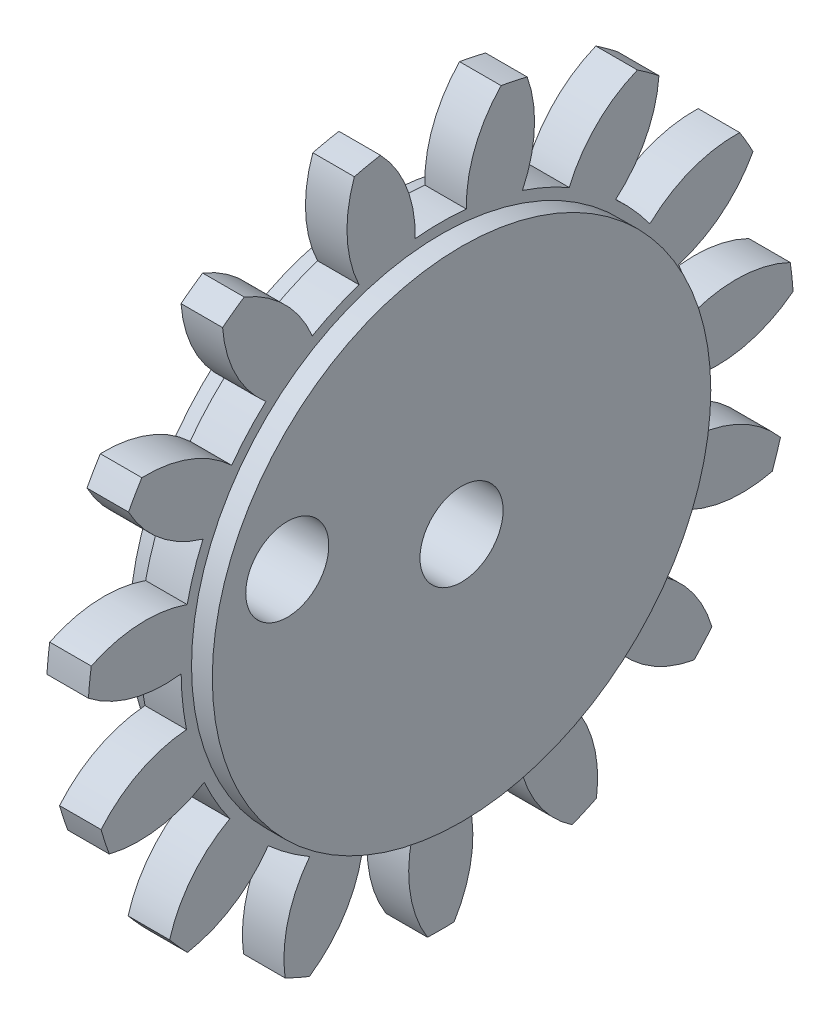
SolidWorks part; units mm, degrees
ref_plane "Plane1" through (0, 0, 0) normal (0, 0, 1) x (1, 0, 0)
ref_plane "Plane2" through (0, 0, 0) normal (0, 1, 0) x (1, 0, 0)
ref_plane "Plane3" through (0, 0, 0) normal (1, 0, 0) x (0, 0, -1)
other "Configuration Table"
sketch "HoldingSke" plane through (0, 0, 0) normal (0, 1, 0) x (1, 0, 0)
  line L0 (0, 0) -> (98.1381, -26.296)
  line L1 (-15, 0) -> (100, 0) construction
  line L2 (0, 0) -> (-2.1039, 2.3779)
  line L3 (0, 0) -> (-11.863, 4.5341)
  line L4 (0, 0) -> (8.3417, 2.2352)
  line L5 (0, 0) -> (-11.8993, -4.4381)
  line L6 (0, 0) -> (-5.2639, -3.5516)
  line L7 (-2.1039, 2.3779) -> (0.6298, 14.7802)
  line L8 (-76.2, 54.61) -> (-61.976, 54.61)
  line L9 (-67.7845, 28.3722) -> (-49.3413, 33.142)
  line L10 (-76.2, 71.12) -> (104.1128, 71.12)
  line L11 (0, 0) -> (-6.35, 0)
  line L12 (-76.2, 101.6) -> (-75.9714, 101.6)
  line L13 (24.9733, 27.94) -> (52.9518, 28.4284)
  line L14 (24.9733, 27.94) -> (24.9746, 27.94)
  line L15 (24.9733, 27.94) -> (100.4006, 29.5858)
  circle A0 centre (0, 0) radius 6.35
  circle A1 centre (0, 0) radius 38.1
  circle A2 centre (0, 0) radius 38.1
  circle A3 centre (0, 0) radius 6.35
  dimension "Num_teeth" = 15
  dimension "H" = 19.05
  dimension "Pitch_radius" = 180.3128
  dimension "Width" = 6.35
  dimension "Thickness" = 6.35
sketch "BasProSke" plane through (0, 0, 0) normal (0, 1, 0) x (1, 0, 0)
  line L0 (-10, 0) -> (60, 0) construction
  line L1 (0, 0) -> (0, 53.975)
  line L2 (0, 0) -> (6.35, 0)
  line L3 (6.35, 0) -> (6.35, 53.975)
  line L4 (6.35, 53.975) -> (0, 53.975)
  dimension "Thickness" = 6.35
  dimension "Diameter" = 107.95
revolve "Base-Revolve" add sketch "BasProSke" angle 360 about L0
sketch "TooCutSke" plane through (0, 0, 0) normal (1, 0, 0) x (0, 0, -1)
  line L1 (0, 0) -> (0, 107) construction
  line L2 (0, 0) -> (-5.3779, 47.3204) construction
  line L3 (0, 0) -> (-19.7119, 92.7371) construction
  line L4 (-5.3779, 47.3204) -> (-9.8559, 46.3685) construction
  arc A0 (3.9155, 39.4926) -> (-3.9155, 39.4926) centre (0, 0) ccw
  arc A1 (9.2414, 53.2038) -> (-9.2414, 53.2038) centre (0, 0) ccw
  circle A2 centre (0, 0) radius 47.625 construction
  circle A3 centre (0, 0) radius 46.108 construction
  arc A4 (-3.9155, 39.4926) -> (-9.2414, 53.2038) centre (-22.9591, 39.9854) ccw
  arc A5 (9.2414, 53.2038) -> (3.9155, 39.4926) centre (22.9591, 39.9854) ccw
extrude "ToothCut" cut sketch "TooCutSke" along normal through all
fillet "Breaks" [suppressed] radius 0.127 tangent propagation no
fillet "RootFillets" [suppressed] radius 1.5888
pattern_circular "TeethCuts" count 15 every 24 about axis through (-10, 0, 0) along (1, 0, 0) of "ToothCut", "RootFillets", "Breaks"
sketch "HubNeaOneSke" plane through (0, 0, 0) normal (-1, 0, 0) x (0, 0, 1)
  circle A0 centre (0, 0) radius 38.1
  dimension "Diameter" = 76.2
extrude "HubNearOne" [suppressed] add sketch "HubNeaOneSke" along normal blind 6.3501
sketch "HubNeaBotSke" plane through (0, 0, 0) normal (-1, 0, 0) x (0, 0, 1)
  circle A0 centre (0, 0) radius 38.1
  dimension "Diameter" = 76.2
extrude "HubNearBoth" add sketch "HubNeaBotSke" along normal blind 3.175
ref_plane "FarPln" through (6.35, 0, 0) normal (1, 0, 0) x (0, 0, -1)
sketch "HubFarSke" plane through (6.35, 0, 0) normal (1, 0, 0) x (0, 0, -1)
  circle A0 centre (0, 0) radius 38.1
  dimension "Diameter" = 76.2
extrude "HubFar" add sketch "HubFarSke" along normal blind 3.175
sketch "BorSke" plane through (0, 0, 0) normal (1, 0, 0) x (0, 0, -1)
  circle A0 centre (0, 0) radius 6.35
  dimension "Diameter" = 12.7
extrude "Bore" cut sketch "BorSke" along normal mid plane 25.4001
sketch "KeySke" plane through (0, 0, 0) normal (1, 0, 0) x (0, 0, -1)
  line L0 (-1.5875, 0) -> (-1.5875, 7.874)
  line L1 (-1.5875, 7.874) -> (1.5875, 7.874)
  line L2 (1.5875, 7.874) -> (1.5875, 0)
  line L3 (0, 0) -> (0, 34) construction
  line L4 (-1.5875, 0) -> (1.5875, 0)
  dimension "Width" = 3.175
extrude "Keyway" [suppressed] cut sketch "KeySke" along normal mid plane 25.4001
pattern_circular "Keyway2" [suppressed] count 2 every 90 about axis through (-10, 0, 0) along (1, 0, 0) reverse direction yes
sketch "Sketch1" plane through (-3.175, 0, 0) normal (-1, 0, 0) x (0, 0, 1)
  line L0 (0, 0) -> (27.6826, 4.2691) construction
  line L1 (0, 0) -> (46.7437, 26.9875) construction
  line L2 (0, 0) -> (37.7438, 12.2637) construction
  circle A0 centre (27.6826, 4.2691) radius 6.35 construction
  arc A1 (47.7296, 25.2029) -> (45.6911, 28.7336) centre (0, 0) ccw construction
  circle A2 centre (0, 0) radius 28.0098 construction
  arc A4 (38.7696, 8.48) -> (36.3498, 15.9277) centre (0, 0) ccw construction
  circle A5 centre (26.6389, 8.6555) radius 6.35
extrude "Cut-Extrude1" cut sketch "Sketch1" against normal through all
equation "' \"Pitch@HoldingSke\" = 4"
equation "' \"Num_teeth@HoldingSke\" = 12"
equation "' \"Ap@HoldingSke\" =  20"
equation "' \"Ap@HoldingSke\" = 20"
equation "' \"Width@HoldingSke\" = 0.5"
equation "' \"Hub_dia@HoldingSke\"= 1"
equation "' \"Hub_dia@HoldingSke\" = 1"
equation "' \"Overall_len@HoldingSke\" = 1.0"
equation "' \"Bore@HoldingSke\" = 0.75"
equation "' \"T_dim@HoldingSke\" = 0.85"
equation "' \"Width@KeySke\" = 0.25"
equation "' \"Show_teeth@HoldingSke\" = 13"
equation "' \"Backlash@HoldingSke\" = 0.009"
equation "' \"Addendum_fac@HoldingSke\" = 1.0"
equation "' \"Dedendum_fac@HoldingSke\" = 1.25"
equation "' \"Dedendum_add@HoldingSke\" = 0.00005"
equation "' \"Clearance_fac@HoldingSke\" = 0.25"
equation "' \"Pitch@HoldingSke\" = 0.5"
equation "' \"Num_teeth@HoldingSke\" = 23"
equation "' \"Show_teeth@HoldingSke\" = 23"
equation "' \"Backlash@HoldingSke\" = 0.0375"
equation "\"Overcut_dia@TooCutSke\" = (\"Num_teeth@HoldingSke\" + 2 * \"Addendum_fac@HoldingSke\") / \"Pitch@HoldingSke\" + 0.002"
equation "\"Pitch_dia@TooCutSke\" = \"Num_teeth@HoldingSke\" / \"Pitch@HoldingSke\""
equation "\"Base_dia@TooCutSke\" = \"Num_teeth@HoldingSke\" / \"Pitch@HoldingSke\" * cos((\"Ap@HoldingSke\"  * 3.14159265 / 180))"
equation "\"Root_dia@TooCutSke\" = (\"Num_teeth@HoldingSke\" + 2) / \"Pitch@HoldingSke\" - 2 * (\"Addendum_fac@HoldingSke\" + \"Dedendum_fac@HoldingSke\") / \"Pitch@HoldingSke\" - \"Dedendum_add@HoldingSke\" * 2"
equation "\"Half_ang@TooCutSke\" = 180 / \"Num_teeth@HoldingSke\""
equation "\"Half_CT@TooCutSke\" = \"Num_teeth@HoldingSke\" / \"Pitch@HoldingSke\" * sin((3.14159265 / 2 / \"Num_teeth@HoldingSke\")) / 2 - 7 * \"Backlash@HoldingSke\" / 4"
equation "\"Flank_rad@TooCutSke\" = \"Num_teeth@HoldingSke\" / \"Pitch@HoldingSke\" / 5"
equation "\"Radius@RootFillets\" = \"Clearance_fac@HoldingSke\" / \"Pitch@HoldingSke\" + \"Dedendum_add@HoldingSke\""
equation "\"Break_rad@Breaks\" = 0.02 / \"Pitch@HoldingSke\""
equation "\"Thickness@HoldingSke\" = \"Width@HoldingSke\""
equation "\"OAL@HoldingSke\" = \"Thickness@HoldingSke\""
equation "\"MHD@HoldingSke\" = (\"Num_teeth@HoldingSke\" + 2) / \"Pitch@HoldingSke\" - 2 * (\"Addendum_fac@HoldingSke\" + \"Dedendum_fac@HoldingSke\")  / \"Pitch@HoldingSke\" - \"Dedendum_add@HoldingSke\" * 2"
equation "\"MBD@HoldingSke\" = (\"Num_teeth@HoldingSke\" + 2) / \"Pitch@HoldingSke\" - 2 * (\"Addendum_fac@HoldingSke\" + \"Dedendum_fac@HoldingSke\")  / \"Pitch@HoldingSke\" - \"Dedendum_add@HoldingSke\" * 2 - 0.002"
equation "\"MHD@HoldingSke\" = ((sgn( \"MHD@HoldingSke\" - \"Hub_dia@HoldingSke\" )-1)*( \"MHD@HoldingSke\" - \"Hub_dia@HoldingSke\" ))/-2+ \"Hub_dia@HoldingSke\""
equation "\"MBD@HoldingSke\" = ((sgn( \"MBD@HoldingSke\" - \"Bore@HoldingSke\" )-1)*( \"MBD@HoldingSke\" - \"Bore@HoldingSke\" ))/-2+ \"Bore@HoldingSke\""
equation "\"OAL@HoldingSke\" = ((sgn( \"OAL@HoldingSke\" - \"Overall_len@HoldingSke\" )+1)*( \"OAL@HoldingSke\" - \"Overall_len@HoldingSke\" ))/2 + \"Overall_len@HoldingSke\" + 0.000002"
equation "\"Num_teeth@TeethCuts\" = int( \"Show_teeth@HoldingSke\" ) + 1"
equation "\"Num_teeth@TeethCuts\" = ((sgn( \"Num_teeth@TeethCuts\" - \"Num_teeth@HoldingSke\" )-1)*( \"Num_teeth@TeethCuts\" - \"Num_teeth@HoldingSke\" ))/-2+ \"Num_teeth@HoldingSke\""
equation "\"Num_teeth@TeethCuts\" = ((sgn( \"Num_teeth@TeethCuts\" - 2.0)+1)*( \"Num_teeth@TeethCuts\" - 2.0))/2 +2.0"
equation "\"Angle@TeethCuts\" = 360.0 / \"Num_teeth@HoldingSke\""
equation "\"Diameter@BasProSke\" = (\"Num_teeth@HoldingSke\" + 2 * \"Addendum_fac@HoldingSke\") / \"Pitch@HoldingSke\""
equation "\"Thickness@BasProSke\"  = \"Thickness@HoldingSke\""
equation "' \"Fillet_rad@BasProSke\" =  \"Thickness@HoldingSke\" * 0.05"
equation "' \"Fillet_rad@BasProSke\" = \"Thickness@HoldingSke\" * 0.05"
equation "\"MHD@HoldingSke\" = ((sgn( \"MHD@HoldingSke\" - \"Root_dia@TooCutSke\" )-1)*( \"MHD@HoldingSke\" - \"Root_dia@TooCutSke\" ))/-2+ \"Root_dia@TooCutSke\""
equation "\"Diameter@HubNeaOneSke\" = \"MHD@HoldingSke\""
equation "\"Length@HubNearOne\" = \"OAL@HoldingSke\" - \"Thickness@BasProSke\""
equation "\"Diameter@HubNeaBotSke\" = \"MHD@HoldingSke\""
equation "\"Length@HubNearBoth\" = ( \"OAL@HoldingSke\" - \"Thickness@BasProSke\" ) / 2.0"
equation "\"Thickness@FarPln\" = \"Thickness@BasProSke\""
equation "\"Diameter@HubFarSke\" = \"MHD@HoldingSke\""
equation "\"Length@HubFar\" = ( \"OAL@HoldingSke\" - \"Thickness@BasProSke\" ) / 2.0"
equation "\"Diameter@BorSke\" = \"MBD@HoldingSke\""
equation "\"D1@Bore\" = \"OAL@HoldingSke\" * 2.0"
equation "\"D1@Keyway\" = \"OAL@HoldingSke\" * 2.0"
equation "\"Offset@KeySke\" = \"T_dim@HoldingSke\" - \"MBD@HoldingSke\" / 2.0"
